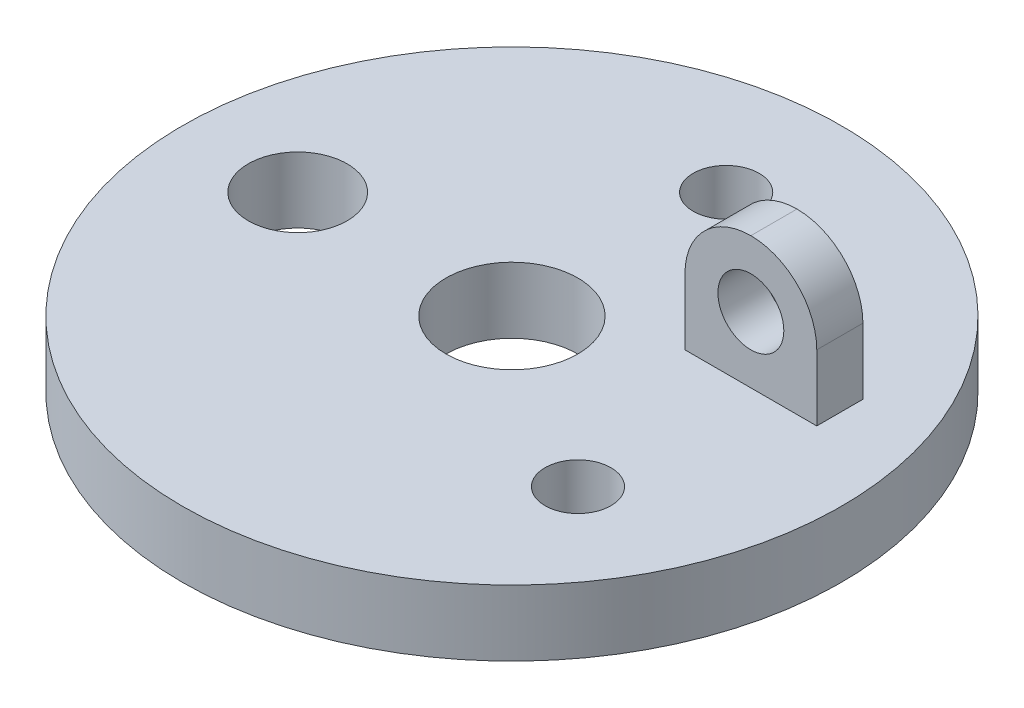
SolidWorks part; units mm, degrees
ref_plane "Front Plane" through (0, 0, 0) normal (0, 0, 1) x (1, 0, 0)
ref_plane "Top Plane" through (0, 0, 0) normal (0, 1, 0) x (1, 0, 0)
ref_plane "Right Plane" through (0, 0, 0) normal (1, 0, 0) x (0, 0, -1)
sketch "Sketch1" plane through (0, 0, 0) normal (0, 1, 0) x (1, 0, 0)
  circle A0 centre (0, 0) radius 50
  circle A1 centre (0, 0) radius 32.5 construction
  circle A2 centre (27.4383, -17.4181) radius 5
  circle A3 centre (-32.5, 0) radius 7.5
  circle A4 centre (0, 32.5) radius 5
  circle A5 centre (0, 0) radius 10
  dimension "D1" = 100
  dimension "D2" = 65
  dimension "D3" = 10
  dimension "D4" = 10
  dimension "D5" = 15
extrude "Boss-Extrude1" add sketch "Sketch1" along normal mid plane 10
sketch "Sketch2" plane through (0, 5, 0) normal (0, 1, 0) x (1, 0, 0)
  line L1 (17.571, 15.6757) -> (37.571, 15.6757)
  line L2 (17.571, 15.6757) -> (17.571, 8.6757)
  line L3 (17.571, 8.6757) -> (37.571, 8.6757)
  line L4 (37.571, 15.6757) -> (37.571, 8.6757)
  line L5 (17.571, 15.6757) -> (37.571, 8.6757) construction
  line L6 (17.571, 8.6757) -> (37.571, 15.6757) construction
  point P0 (27.571, 12.1757)
extrude "Boss-Extrude2" add sketch "Sketch2" along normal blind 20
fillet "Fillet1" radius 10 2 edges at (17.571, 25, -12.1757) (37.571, 25, -12.1757)
sketch "Sketch3" plane through (0, 0, -8.6757) normal (0, 0, 1) x (1, 0, 0)
  circle A0 centre (27.571, 15) radius 5
  dimension "D1" = 10
extrude "Cut-Extrude1" cut sketch "Sketch3" against normal through all
